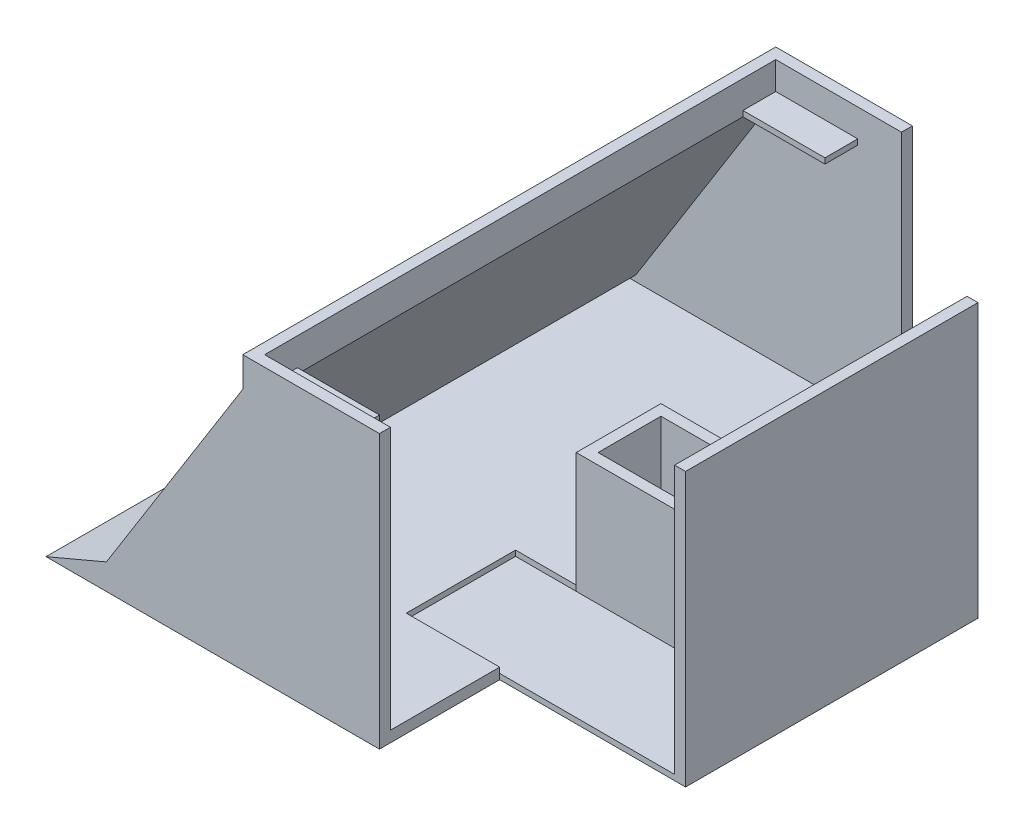
SolidWorks part; units mm, degrees
ref_plane "Alzado" through (0, 0, 0) normal (0, 0, 1) x (1, 0, 0)
ref_plane "Planta" through (0, 0, 0) normal (0, 1, 0) x (1, 0, 0)
ref_plane "Vista lateral" through (0, 0, 0) normal (1, 0, 0) x (0, 0, -1)
sketch "Croquis1" plane through (0, 0, 0) normal (0, 0, 1) x (1, 0, 0)
  line L0 (0, 0) -> (94.9987, 0)
  line L1 (94.9987, 0) -> (94.9987, 50)
  line L2 (94.9987, 50) -> (35.9987, 50)
  line L3 (35.9987, 50) -> (35.9987, 44.518)
  line L4 (0, 0) -> (11.0461, 4.6888)
  line L5 (35.9987, 44.518) -> (11.0461, 4.6888)
  dimension "D1" = 23
extrude "Saliente-Extruir1" add sketch "Croquis1" along normal blind 97.5
shell "Vaciado1" thickness 2 removed face at (65.4987, 50, 48.75)
sketch "Croquis2" plane through (0, 50, 0) normal (0, 1, 0) x (1, 0, 0)
  line L0 (-27.5, 0) -> (27.5, 0) construction
  line L1 (60.9987, 0) -> (94.9987, 0)
  line L2 (60.9987, 0) -> (60.9987, -22)
  line L3 (60.9987, -22) -> (94.9987, -22)
  line L4 (94.9987, 0) -> (94.9987, -22)
  line L5 (94.9987, -97.5) -> (94.9987, 0) construction
  line L6 (94.9987, -97.5) -> (35.9987, -97.5) construction
  line L7 (94.9987, -75.5) -> (60.9987, -75.5)
  line L8 (94.9987, -75.5) -> (94.9987, -97.5)
  line L9 (94.9987, -97.5) -> (60.9987, -97.5)
  line L10 (60.9987, -75.5) -> (60.9987, -97.5)
  dimension "D1" = 34
  dimension "D2" = 22
  dimension "D3" = 22
  dimension "D4" = 34
extrude "Cortar-Extruir1" cut sketch "Croquis2" against normal through all and the other way through all
sketch "Croquis3" plane through (0, 50, 0) normal (0, 1, 0) x (1, 0, 0)
  line L0 (0, -48.75) -> (92.9987, -48.75) construction
  line L1 (0, -97.5) -> (0, 0) construction
  line L2 (92.9987, -75.5) -> (92.9987, -22) construction
sketch "Croquis5" plane through (0, 2, 0) normal (0, 1, 0) x (1, 0, 0)
  line L0 (0, -48.75) -> (92.9987, -48.75) construction
  line L1 (92.9987, -75.5) -> (92.9987, -22) construction
  line L2 (55.9987, -56.5) -> (92.9987, -56.5)
  line L3 (55.9987, -56.5) -> (55.9987, -41)
  line L4 (55.9987, -41) -> (92.9987, -41)
  line L5 (92.9987, -56.5) -> (92.9987, -41)
  line L6 (55.9987, -56.5) -> (92.9987, -41) construction
  line L7 (55.9987, -41) -> (92.9987, -56.5) construction
  point P4 (74.4987, -48.75)
  dimension "D1" = 37
  dimension "D2" = 15.5
extrude "Saliente-Extruir3" add sketch "Croquis5" along normal blind 22
sketch "Croquis7" plane through (0, 0, 56.5) normal (0, 0, 1) x (1, 0, 0)
  line L0 (94.9987, 13.15) -> (82.7787, 13.15) construction
  line L2 (94.9987, 0) -> (94.9987, 50) construction
  line L3 (82.7787, 13.15) -> (82.7787, 0) construction
  line L4 (94.9987, 0) -> (60.9987, 0) construction
  circle A0 centre (82.7787, 13.15) radius 4.75
  dimension "D3" = 9.5
  dimension "D1" = 12.22
  dimension "D2" = 13.15
extrude "Cortar-Extruir2" cut sketch "Croquis7" against normal blind 22
shell "Vaciado2" thickness 2 removed face at (74.4987, 24, 48.75)
sketch "Croquis9" plane through (0, 2, 0) normal (0, 1, 0) x (1, 0, 0)
  line L0 (60.9987, -22) -> (92.9987, -22) construction
  line L1 (43.9087, -22) -> (92.9987, -22)
  line L2 (43.9087, -22) -> (43.9087, -42)
  line L3 (43.9087, -42) -> (92.9987, -42)
  line L4 (92.9987, -22) -> (92.9987, -42)
  line L5 (92.9987, -41) -> (92.9987, -22) construction
  line L7 (43.9087, -55.5) -> (92.9987, -55.5)
  line L8 (43.9087, -55.5) -> (43.9087, -75.5)
  line L9 (43.9087, -75.5) -> (92.9987, -75.5)
  line L10 (92.9987, -55.5) -> (92.9987, -75.5)
  line L11 (43.9087, -55.5) -> (92.9987, -75.5) construction
  line L12 (43.9087, -75.5) -> (92.9987, -55.5) construction
  point P8 (68.4537, -65.5)
  dimension "D1" = 20
  dimension "D2" = 49.09
  dimension "D3" = 20
  dimension "D4" = 49.09
extrude "Cortar-Extruir3" cut sketch "Croquis9" against normal blind 1
sketch "Croquis11" plane through (0, 0, 95.5) normal (0, 0, -1) x (-1, 0, 0)
  line L2 (-37.9987, 43.9432) -> (-52.9987, 43.9432)
  line L3 (-52.9987, 43.9432) -> (-52.9987, 44.9432)
  line L4 (-52.9987, 44.9432) -> (-37.9987, 44.9432)
  line L5 (-37.9987, 50) -> (-37.9987, 43.9432) construction
  line L10 (-60.9987, 50) -> (-60.9987, 2)
  line L11 (-60.9987, 2) -> (-9.8303, 2)
  line L12 (-9.8303, 2) -> (-12.4068, 3.0937)
  line L13 (-12.4068, 3.0937) -> (-37.9987, 43.9432)
  line L14 (-37.9987, 43.9432) -> (-37.9987, 50)
  line L15 (-37.9987, 50) -> (-60.9987, 50)
  line L20 (-37.9987, 43.9432) -> (-37.9987, 44.9432)
  dimension "D1" = 15
  dimension "D2" = 1
  dimension "D3" = 0
extrude "Saliente-Extruir7" add sketch "Croquis11" along normal blind 6
ref_plane "Plano2" through (37.9987, 50, 2) normal (-1, 0, 0) x (0, 0, 1)
sketch "Croquis15" plane through (0, 0, 2) normal (0, 0, 1) x (1, 0, 0)
  line L2 (37.9987, 50) -> (37.9987, 43.9432) construction
  line L3 (37.9987, 44.94) -> (52.9987, 44.94)
  line L4 (37.9987, 44.94) -> (37.9987, 43.94)
  line L5 (37.9987, 43.94) -> (52.9987, 43.94)
  line L6 (52.9987, 44.94) -> (52.9987, 43.94)
  dimension "D1" = 15
  dimension "D2" = 1
extrude "Saliente-Extruir8" add sketch "Croquis15" along normal blind 6
sketch "Croquis18" plane through (5.8231, -3.6481, 0) normal (-0.8474, 0.5309, 0) x (0, 0, 1)
  spline S0 degree 3 number of poles 7382 (42.4246, 45.8091) -> (42.4246, 45.8091)
  spline S1 degree 3 number of poles 726 (40.72, 24.9285) -> (40.72, 24.9285)
  spline S2 degree 3 number of poles 420 (36.757, 34.7806) -> (36.757, 34.7806)
  spline S3 degree 3 poles (34.5514, 35.1408) (34.3287, 34.9223) (34.1239, 34.687) (33.9382, 34.4362) (33.8765, 34.3528) (33.7574, 34.1827) (34.7775, 35.355) (34.6255, 35.2135) (34.5514, 35.1408) (34.3287, 34.9223) (34.1239, 34.687) knots -0.166667 0 0 0 0.5 0.5 0.5 0.666667 0.833333 1 1 1 1.5 1.5 1.5 weights 1 0.99793 0.99793 1 1 1 1 1 1 0.99793 0.99793 only from (34.5514, 35.1408) to (34.5514, 35.1408)
  spline S4 degree 3 number of poles 724 (41.4399, 28.6975) -> (41.4399, 28.6975)
  spline S5 degree 3 number of poles 585 (34.5514, 35.1408) -> (34.5514, 35.1408)
  spline S6 degree 3 number of poles 670 (47.6391, 21.0023) -> (47.6391, 21.0023)
  spline S7 degree 3 number of poles 870 (40.2948, 46.6768) -> (40.2948, 46.6768)
  spline S8 degree 3 number of poles 490 (48.9193, 50.9288) -> (48.9193, 50.9288)
  spline S9 degree 3 number of poles 302 (51.9539, 50.1421) -> (51.9539, 50.1421)
  spline S10 degree 3 number of poles 834 (50.3092, 54.1417) -> (50.3092, 54.1417)
  spline S11 degree 3 number of poles 254 (53.5354, 53.8371) -> (53.5354, 53.8371)
  spline S12 degree 3 number of poles 3208 (45.3496, 38.4125) -> (45.3496, 38.4125)
  spline S13 degree 3 number of poles 210 (60.1456, 48.7103) -> (60.1456, 48.7103)
  spline S14 degree 3 number of poles 457 (55.6985, 40.1976) -> (55.6985, 40.1976)
  spline S15 degree 3 number of poles 198 (58.4679, 36.0409) -> (58.4679, 36.0409)
  spline S16 degree 3 number of poles 271 (53.9676, 34.9518) -> (53.9676, 34.9518)
  spline S17 degree 3 number of poles 146 (56.7977, 40.549) -> (56.7977, 40.549)
  point P18 (0, 0)
